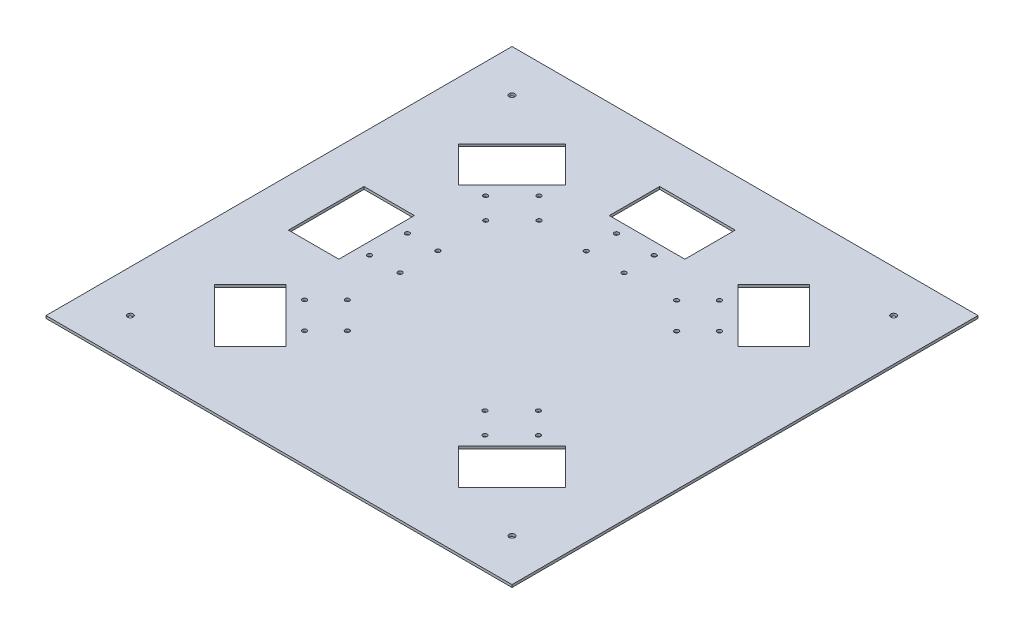
SolidWorks part; units mm, degrees
ref_plane "Front Plane" through (0, 0, 0) normal (0, 0, 1) x (1, 0, 0)
ref_plane "Top Plane" through (0, 0, 0) normal (0, 1, 0) x (1, 0, 0)
ref_plane "Right Plane" through (0, 0, 0) normal (1, 0, 0) x (0, 0, -1)
sketch "Sketch1" plane through (0, 0, 0) normal (0, 1, 0) x (1, 0, 0)
  line L1 (-70.7304, 107.3765) -> (70.7304, 107.3765)
  line L2 (-107.5, 70.607) -> (-107.5, -70.607)
  line L3 (-70.6996, -107.4074) -> (70.7613, -107.4074)
  line L4 (107.5, 70.607) -> (107.5, -70.8539)
  line L5 (-89.7907, 89.7907) -> (89.1307, -89.1307) construction
  line L6 (-89.0535, -89.0535) -> (89.0535, 89.0535) construction
  line L7 (107.5, 70.607) -> (70.7304, 107.3765)
  line L8 (70.7613, -107.4074) -> (107.5, -70.8539)
  line L9 (-107.5, -70.607) -> (-70.6996, -107.4074)
  line L14 (-70.7304, 107.3765) -> (-107.5, 70.607)
  line L15 (-103.2574, 74.8496) -> (-74.9731, 103.1339)
  line L16 (-185, 185) -> (185, -185) construction
  line L17 (-185, 185) -> (185, 185)
  line L18 (-185, 185) -> (-185, -185)
  line L19 (-185, -185) -> (185, -185)
  line L20 (185, 185) -> (185, -185)
  line L21 (185, 185) -> (-185, -185) construction
  line L22 (-89.7907, 89.7907) -> (-103.2574, 103.2574) construction
  line L23 (-89.1152, 88.9917) -> (-118.075, 118.075) construction
  line L24 (-118.075, 118.075) -> (-139.2835, 96.8665) construction
  line L25 (-139.2835, 96.8665) -> (-96.8597, 139.2903) construction
  line L26 (-139.2835, 96.8665) -> (-96.8597, 139.2903)
  line L27 (-139.2835, 96.8665) -> (-110.9992, 68.5823)
  line L28 (0, 0) -> (-107.5, 0) construction
  line L29 (-64.5, 19.656) -> (-64.5, -20.344)
  line L30 (-64.5, 19.656) -> (-107.5, 19.656)
  line L31 (-96.8597, 139.2903) -> (-68.5754, 111.006)
  line L32 (-110.9992, 68.5823) -> (-68.5754, 111.006)
  line L33 (96.8665, 139.2835) -> (139.2903, 96.8597)
  line L34 (-64.5, -20.344) -> (-107.5, -20.344)
  line L35 (-107.5, 19.656) -> (-107.5, -20.344)
  line L36 (-64.5, 19.656) -> (-107.5, -20.344) construction
  line L37 (139.2903, 96.8597) -> (111.006, 68.5754)
  line L38 (68.5823, 110.9992) -> (111.006, 68.5754)
  line L39 (96.8665, 139.2835) -> (68.5823, 110.9992)
  line L40 (-64.5, -20.344) -> (-107.5, 19.656) construction
  line L41 (-107.5, -20.344) -> (-107.5, -15.064) construction
  line L42 (-107.5, -15.064) -> (-97.9995, -15.064) construction
  line L47 (-107.5, 70.607) -> (-107.5, 0) construction
  line L52 (19.7795, 64.3765) -> (19.7795, 107.3765)
  line L53 (19.7795, 64.3765) -> (-20.2205, 64.3765)
  line L59 (-103.2574, 74.8496) -> (-72.8518, 44.444)
  line L61 (-72.8518, 44.444) -> (-44.5675, 72.7283)
  line L62 (-99.5238, 78.5831) -> (-92.8063, 71.8656)
  line L63 (44.444, 72.8518) -> (72.7283, 44.5675)
  line L64 (-74.9731, 103.1339) -> (-72.8518, 44.444) construction
  line L65 (-103.2574, 74.8496) -> (-44.5675, 72.7283) construction
  line L66 (-74.9731, 103.1339) -> (-44.5675, 72.7283)
  line L67 (103.1339, 74.9731) -> (72.7283, 44.5675)
  line L68 (74.8496, 103.2574) -> (44.444, 72.8518)
  line L69 (72.8518, -44.444) -> (44.5675, -72.7283)
  line L70 (74.9731, -103.1339) -> (44.5675, -72.7283)
  line L71 (103.2574, -74.8496) -> (72.8518, -44.444)
  line L72 (-44.444, -72.8518) -> (-72.7283, -44.5675)
  line L73 (-103.1339, -74.9731) -> (-72.7283, -44.5675)
  line L74 (-74.8496, -103.2574) -> (-44.444, -72.8518)
  line L75 (-20.2205, 64.3765) -> (-20.2205, 107.3765)
  line L76 (0, -0.1235) -> (-64.5, 19.656) construction
  line L77 (-107.5, 0) -> (-185, 0) construction
  line L82 (-107.5, 0) -> (-158.075, 0) construction
  line L83 (-107.5, 0) -> (-138.075, 0) construction
  line L88 (-107.5, 0) -> (-127.5, 0) construction
  line L89 (-65.0737, 107.3765) -> (-0.1337, 107.3765) construction
  line L93 (-147.5, 30) -> (-107.5, 30)
  line L95 (-65.0737, 107.3765) -> (-47.5362, 107.3765) construction
  line L96 (-147.5, 30) -> (-147.5, -30)
  line L97 (-147.5, -30) -> (-107.5, -30)
  line L98 (-107.5, 30) -> (-107.5, -30)
  line L99 (-147.5, 30) -> (-107.5, -30) construction
  line L100 (-147.5, -30) -> (-107.5, 30) construction
  line L101 (-0.1337, 107.3765) -> (-0.1337, 185) construction
  line L102 (-0.1337, 107.3765) -> (-0.1337, 127.3765) construction
  line L103 (-107.5, 70.607) -> (-110.3285, 67.7785) construction
  line L104 (-30.1337, 147.3765) -> (29.8663, 147.3765)
  line L105 (-30.1337, 147.3765) -> (-30.1337, 107.3765)
  line L106 (-30.1337, 107.3765) -> (29.8663, 107.3765)
  line L107 (29.8663, 147.3765) -> (29.8663, 107.3765)
  line L108 (-30.1337, 147.3765) -> (29.8663, 107.3765) construction
  line L109 (-30.1337, 107.3765) -> (29.8663, 147.3765) construction
  line L110 (-70.7304, 107.3765) -> (-67.9021, 110.2049) construction
  line L111 (-67.9021, 110.2049) -> (-110.3285, 67.7785)
  line L112 (139.2835, -96.8665) -> (96.8597, -139.2903)
  line L113 (96.8597, -139.2903) -> (68.5754, -111.006)
  line L114 (110.9992, -68.5823) -> (68.5754, -111.006)
  line L115 (139.2835, -96.8665) -> (110.9992, -68.5823)
  line L116 (-96.8665, -139.2835) -> (-139.2903, -96.8597)
  line L117 (-139.2903, -96.8597) -> (-111.006, -68.5754)
  line L118 (-68.5823, -110.9992) -> (-111.006, -68.5754)
  line L119 (-96.8665, -139.2835) -> (-68.5823, -110.9992)
  line L120 (185, 185) -> (118.0784, 118.0716) construction
  line L121 (-185, 185) -> (-151.5362, 151.5362) construction
  line L122 (185, 185) -> (151.5362, 151.5362) construction
  line L123 (185, -185) -> (151.5362, -151.5362) construction
  line L124 (-185, -185) -> (-151.5362, -151.5362) construction
  circle A25 centre (-92.8063, 71.8656) radius 1.75
  circle A26 centre (-75.8358, 54.895) radius 1.75
  circle A27 centre (-71.5931, 93.0788) radius 1.75
  circle A28 centre (-54.6226, 76.1082) radius 1.75
  circle A29 centre (76.1082, 54.6226) radius 1.75
  circle A30 centre (93.0788, 71.5931) radius 1.75
  circle A31 centre (54.895, 75.8358) radius 1.75
  circle A32 centre (71.8656, 92.8063) radius 1.75
  circle A33 centre (54.6226, -76.1082) radius 1.75
  circle A34 centre (71.5931, -93.0788) radius 1.75
  circle A35 centre (75.8358, -54.895) radius 1.75
  circle A36 centre (92.8063, -71.8656) radius 1.75
  circle A37 centre (-76.1082, -54.6226) radius 1.75
  circle A38 centre (-93.0788, -71.5931) radius 1.75
  circle A39 centre (-54.895, -75.8358) radius 1.75
  circle A40 centre (-71.8656, -92.8063) radius 1.75
  circle A41 centre (-97.9995, -15.064) radius 1.75
  circle A42 centre (-97.9995, 14.936) radius 1.75
  circle A43 centre (-73.9309, 15.0595) radius 1.75
  circle A44 centre (-73.9309, -14.9405) radius 1.75
  circle A45 centre (15.0595, 97.876) radius 1.75
  circle A46 centre (15.183, 73.8074) radius 1.75
  circle A47 centre (-14.9405, 97.876) radius 1.75
  circle A48 centre (-14.817, 73.8074) radius 1.75
  circle A49 centre (-151.5362, -151.5362) radius 2.25
  circle A50 centre (151.5362, -151.5362) radius 2.25
  circle A51 centre (151.5362, 151.5362) radius 2.25
  circle A52 centre (-151.5362, 151.5362) radius 2.25
  point P0 (0, 0)
  point P9 (-89.1152, 89.1152)
  point P18 (0, 0)
  point P19 (-89.1152, 88.9917)
  point P30 (0, 0)
  point P34 (0, 0)
  point P39 (-117.2477, 117.2477)
  point P42 (-118.075, 0.0028)
  point P46 (-86, -0.344)
  point P98 (-0.1496, 0.0261)
  point P148 (0, 0)
  dimension "D5" = 40
  dimension "D6" = 9.5
  dimension "D10" = 4
  dimension "D11" = 3.5
  dimension "D12" = 24
  dimension "D9" = 17.5375
  dimension "D17" = 3.5
  dimension "D19" = 30
  dimension "D20" = 3.5
  dimension "D25" = 30
  dimension "D26" = 2
  dimension "D35" = 4.5
  dimension "D36" = 4.5
  dimension "D37" = 4.5
  dimension "D38" = 4.5
  dimension "D1" = 141.4609
  dimension "D2" = 215
  dimension "D3" = 52
  dimension "D7" = 40
  dimension "D8" = 5.28
  dimension "D13" = 47.325
  dimension "D4" = 40
  dimension "D14" = 370
  dimension "D15" = 370
  dimension "D16" = 43
  dimension "D18" = 30
  dimension "D22" = 43
  dimension "D23" = 20
  dimension "D24" = 5.28
  dimension "D27" = 67.4646
  dimension "D28" = 60
  dimension "D29" = 64.94
  dimension "D30" = 20
  dimension "D31" = 60
  dimension "D32" = 47.325
  dimension "D33" = 47.325
  dimension "D34" = 47.325
  dimension "D21" = 4
extrude "Boss-Extrude2" add sketch "Sketch1" along normal blind 2 contours L9 L74 L72 L73 A40 A39 A38 A37 | L7 L68 L63 L67 A32 A31 A30 A29 | L53 L75 L1 L14 L66 L61 L59 L2 L30 L29 L34 L9 L73 L72 L74 L3 L8 L4 L7 L67 L63 L68 L52 A36 A35 A34 A33 | L75 L53 L52 L1 A48 A47 A46 A45 | A25 L15 L14 L59 L61 L66 A28 A27 A26 | L20 L17 L18 L19 L119 L116 L117 L118 L115 L112 L113 L114 L39 L33 L37 L38 L32 L27 L26 L31 L104 L107 L1 L7 L4 L8 L3 L9 L2 L97 L96 L93 L14 L15 | L34 L29 L30 L2 A44 A43 A42 A41 region at (7.8394, 0, 7.8112) region at (-73.917, 0, -73.7844) region at (-0.2283, 0, -85.8773) region at (73.7844, 0, -73.917) region at (-86.0008, 0, 0.3518) region at (-73.7844, 0, 73.917) region at (0, 0, -179.7674)
